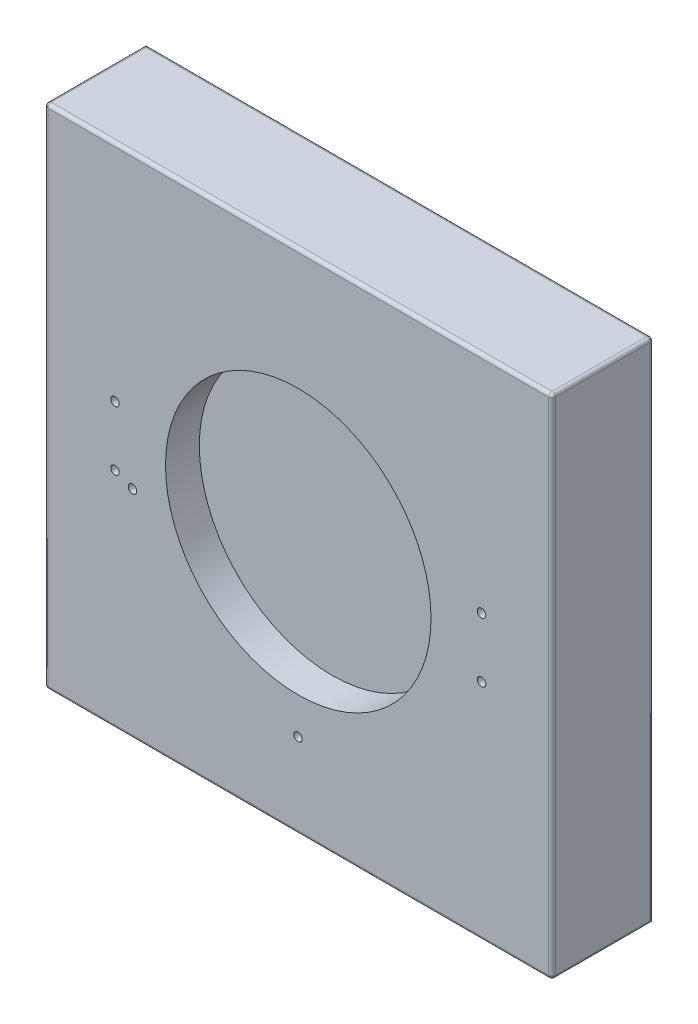
SolidWorks part; units mm, degrees
material "PLA"
ref_plane "Front Plane" through (0, 0, 0) normal (0, 0, 1) x (1, 0, 0)
ref_plane "Top Plane" through (0, 0, 0) normal (0, 1, 0) x (1, 0, 0)
ref_plane "Right Plane" through (0, 0, 0) normal (1, 0, 0) x (0, 0, -1)
sketch "Sketch1" plane through (0, 0, 0) normal (0, 0, 1) x (1, 0, 0)
  line L1 (-75, -75) -> (75, -75)
  line L2 (-75, -75) -> (-75, 75)
  line L3 (-75, 75) -> (75, 75)
  line L4 (75, -75) -> (75, 75)
  line L5 (-75, -75) -> (75, 75) construction
  line L6 (-75, 75) -> (75, -75) construction
  point P0 (0, 0)
  dimension "D1" = 150
  dimension "D2" = 150
extrude "Boss-Extrude1" add sketch "Sketch1" against normal blind 30 contours L2 L3 L4 L1
sketch "Sketch2" plane through (0, 0, 0) normal (0, 0, 1) x (1, 0, 0)
  circle A0 centre (0, 0) radius 39.25
  dimension "D1" = 78.5
fillet "Fillet1" radius 1 10 edges at (75, -75, -15) (-75, -75, -15) (-75, 75, -15) (75, 0, -30) (0, 75, -30) (75, 75, -15) (0, -75, 0) (-75, 0, 0) (75, 0, 0) (0, 75, 0)
sketch "Sketch7" plane through (0, 0, 0) normal (0, 1, 0) x (1, 0, 0)
  line L1 (-39.7685, 40.3246) -> (-29.7685, 40.3246)
  line L2 (-39.7685, 40.3246) -> (-39.7685, 30.3246)
  line L3 (-39.7685, 30.3246) -> (-29.7685, 30.3246)
  line L4 (-29.7685, 40.3246) -> (-29.7685, 30.3246)
  dimension "D1" = 10
  dimension "D2" = 10
ref_axis "Axis2" through (0, 0, 0) along (0, 0, -1)
extrude "Cut-Extrude4" cut sketch "Sketch2" against normal blind 10 contours A0
sketch "Sketch10" plane through (-75, 0, 0) normal (-1, 0, 0) x (0, 0, 1)
  line L0 (-30, 0) -> (0, 0) construction
  line L1 (-30, -74) -> (-30, 74) construction
sketch "Sketch19" plane through (0, 0, -30) normal (0, 0, -1) x (-1, 0, 0)
  line L0 (0.5, 74) -> (0, -75) construction
  line L1 (75, 74) -> (-74, 74) construction
  line L2 (74, -75) -> (-74, -75) construction
sketch "Sketch20" plane through (75, 0, 0) normal (1, 0, 0) x (0, 0, -1)
  line L0 (1, 0) -> (30, 0) construction
  line L1 (1, 74) -> (1, -74) construction
  line L2 (30, 0) -> (0, 0) construction
sketch "Sketch21" plane through (0, 0, 0) normal (0, 0, 1) x (1, 0, 0)
  circle A0 centre (54.1909, 8.8) radius 1.5
  circle A1 centre (54.1909, -8.8) radius 1.5
  circle A2 centre (-54.1909, 8.8) radius 1.5
  circle A3 centre (-54.1909, -8.8) radius 1.5
hole_wizard "Tap Drill for M3x0.5 Tap2" positions "Sketch22" profile "Sketch23" hole size "M3x0.5" standard "ANSI Metric" end condition through all
sketch "Sketch22" plane through (0, 0, 0) normal (0, 0, 1) x (1, 0, 0)
  point P0 (-54.1909, -8.8)
  point P3 (-54.1909, 8.8)
  point P6 (54.1909, -8.8)
  point P9 (54.1909, 8.8)
sketch "Sketch23" plane through (-54.1909, -8.8, 0) normal (1, 0, 0) x (0, -1, 0)
  line L0 (0, 0) -> (0, 30)
  line L1 (0, 30) -> (1.25, 30)
  line L2 (1.25, 30) -> (1.25, 0)
  line L5 (1.25, 0) -> (0, 0)
  line L11 (0, -6.35) -> (0, 107.95) construction
  dimension "Thru Hole Dia." = 2.5
  dimension "Thru Hole Depth" = 30
hole_wizard "Tap Drill for M3x0.5 Tap3" positions "Sketch25" profile "Sketch26" hole size "M3x0.5" standard "ANSI Metric" end condition through all
sketch "Sketch25" plane through (0, 0, 0) normal (0, 0, 1) x (1, 0, 0)
  line L0 (74, -75) -> (-74, -75) construction
  line L1 (-75, -74) -> (-75, 74) construction
  point P0 (-49, -11)
  dimension "D1" = 64
  dimension "D2" = 26
sketch "Sketch26" plane through (-49, -11, 0) normal (1, 0, 0) x (0, -1, 0)
  line L0 (0, 0) -> (0, 30)
  line L1 (0, 30) -> (1.25, 30)
  line L2 (1.25, 30) -> (1.25, 0)
  line L5 (1.25, 0) -> (0, 0)
  line L11 (0, -6.35) -> (0, 107.95) construction
  dimension "Thru Hole Dia." = 2.5
  dimension "Thru Hole Depth" = 30
hole_wizard "Tap Drill for M3x0.5 Tap5" positions "Sketch29" profile "Sketch30" hole size "M3x0.5" standard "ANSI Metric" end condition through all
sketch "Sketch29" plane through (0, 0, 0) normal (0, 0, 1) x (1, 0, 0)
  line L0 (-0.5, 74) -> (0, -75) construction
  circle A0 centre (-0.0839, -50) radius 3.4421
  point P0 (-0.0839, -50)
  point P9 (0, 0)
sketch "Sketch30" plane through (-0.0839, -50, 0) normal (1, 0, 0) x (0, -1, 0)
  line L0 (0, 0) -> (0, 30)
  line L1 (0, 30) -> (1.25, 30)
  line L2 (1.25, 30) -> (1.25, 0)
  line L5 (1.25, 0) -> (0, 0)
  line L11 (0, -6.35) -> (0, 107.95) construction
  dimension "Thru Hole Dia." = 2.5
  dimension "Thru Hole Depth" = 30
